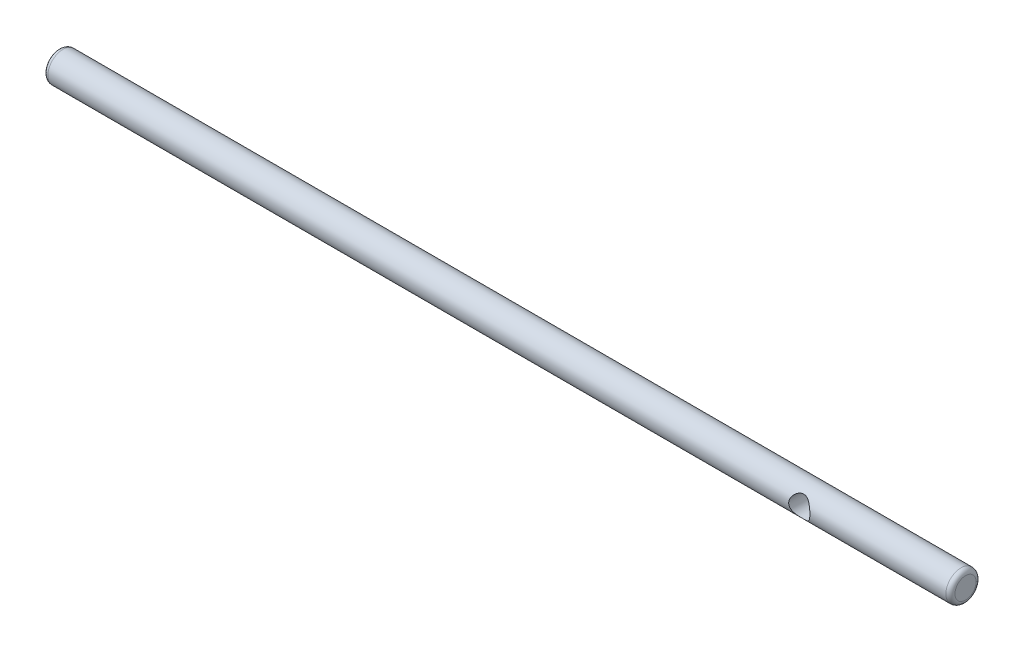
SolidWorks part; units mm, degrees
ref_plane "Ebene vorne" through (0, 0, 0) normal (0, 0, 1) x (1, 0, 0)
ref_plane "Ebene oben" through (0, 0, 0) normal (0, 1, 0) x (1, 0, 0)
ref_plane "Ebene rechts" through (0, 0, 0) normal (1, 0, 0) x (0, 0, -1)
sketch "Skizze1" plane through (0, 0, 0) normal (0, 0, 1) x (1, 0, 0)
  line L1 (0, 0) -> (-150, 0)
  line L2 (0, 0) -> (0, 2.5)
  line L3 (0, 2.5) -> (-150, 2.5)
  line L4 (-150, 0) -> (-150, 2.5)
  dimension "D1" = 2.5
  dimension "D2" = 150
revolve "Rotation1" add sketch "Skizze1" angle 360 about L1
fillet "Verrundung1" radius 0.75 1 edges at (-150, 2.5, 0)
fillet "Verrundung2" radius 0.75 1 edges at (0, 2.5, 0)
hole_wizard "Ø3.5 (3.5) Durchmesser Bohrung1" positions "3D-Skizze2" profile "Skizze3" hole size "Ø3.5" standard "DIN" end condition through all
sketch3d "3D-Skizze2"
  point P0 (-25, 0.063, 2.4992)
  dimension "D1" = 25
sketch "Skizze3" plane through (-25, 0.063, 2.4992) normal (1, 0, 0) x (0, -0.9997, 0.0252)
  line L0 (0, 0) -> (0, 5.0622)
  line L1 (0, 5.0622) -> (1.75, 5.0622)
  line L2 (1.75, 5.0622) -> (1.75, 0)
  line L5 (1.75, 0) -> (0, 0)
  line L11 (0, -6.35) -> (0, 107.95) construction
  dimension "Bohrerdurchmesser" = 3.5
  dimension "Bohrungstiefe" = 5.0622
